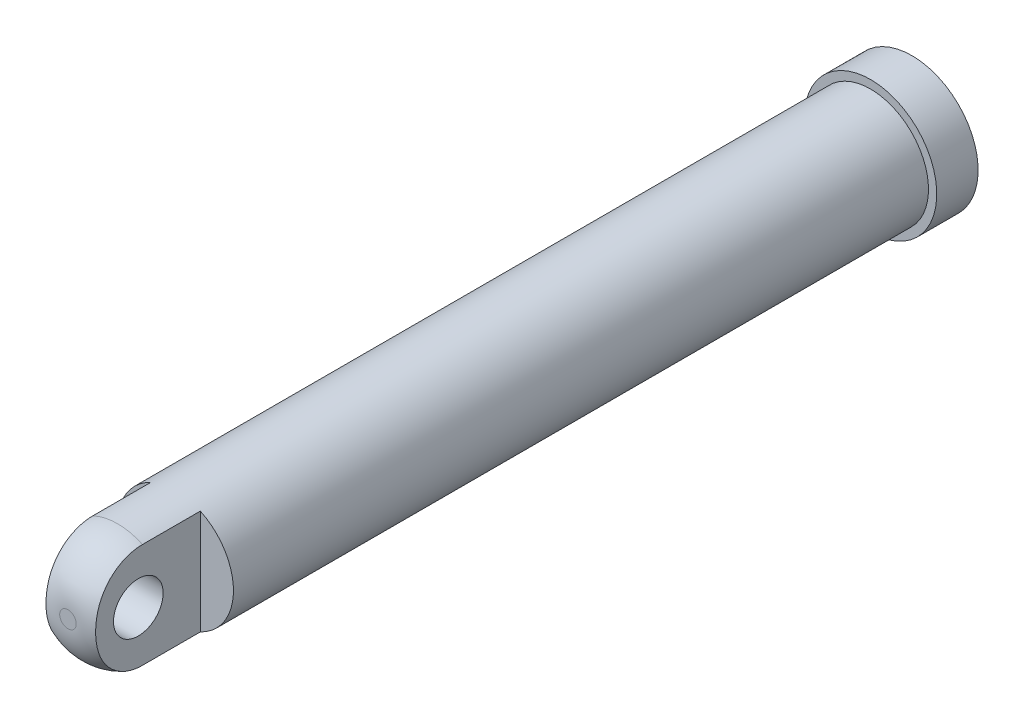
SolidWorks part; units mm, degrees
ref_plane "前视基准面" through (0, 0, 0) normal (0, 0, 1) x (1, 0, 0)
ref_plane "上视基准面" through (0, 0, 0) normal (0, 1, 0) x (1, 0, 0)
ref_plane "右视基准面" through (0, 0, 0) normal (1, 0, 0) x (0, 0, -1)
sketch "草图1" plane through (0, 0, 0) normal (0, 0, 1) x (1, 0, 0)
  circle A0 centre (0, 0) radius 70
extrude "凸台-拉伸2" add sketch "草图1" along normal blind 1150
sketch "草图2" plane through (0, 0, 1150) normal (0, 0, 1) x (1, 0, 0)
  line L0 (-30, 70) -> (-124.0556, 32.9777)
  line L1 (-30, 70) -> (-30, -70)
  line L2 (30, 70) -> (30, -70)
  line L4 (30, 70) -> (102.0705, 29.2659)
  line L5 (102.0705, 29.2659) -> (78.3722, -60.6733)
  line L6 (78.3722, -60.6733) -> (30, -70)
  line L7 (30, -70) -> (29.5481, -69.8099)
  line L8 (-30, -70) -> (-96.5186, -70)
  line L9 (-96.5186, -70) -> (-124.0556, 32.9777)
  circle M1 centre (0, 0) radius 70
extrude "切除-拉伸1" cut sketch "草图2" against normal blind 130 contours L2 M1 | L1 M1 region at (-46.4707, 0, 1150) region at (46.4707, 0, 1150)
sketch "草图3" plane through (30, 0, 0) normal (1, 0, 0) x (0, 0, -1)
  line L0 (-1150, 63.2456) -> (-1150, -63.2456) construction
  circle A0 centre (-1095, 0) radius 30
  point P2 (-1150, 0)
  dimension "D1" = 55
extrude "切除-拉伸2" cut sketch "草图3" against normal blind 130
fillet "圆角1" radius 60 1 edges at (0, 70, 1150)
sketch "草图4" plane through (0, 0, 0) normal (0, 0, -1) x (-1, 0, 0)
  circle A0 centre (0, 0) radius 50
extrude "切除-拉伸3" cut sketch "草图4" against normal blind 977
sketch "草图5" plane through (0, 0, 0) normal (0, 0, -1) x (-1, 0, 0)
  circle A0 centre (0, 0) radius 79.8496
extrude "切除-拉伸4" cut sketch "草图5" against normal blind 100
sketch "草图6" plane through (0, 0, 100) normal (0, 0, -1) x (-1, 0, 0)
  circle A0 centre (0, 0) radius 77.9741
extrude "切除-拉伸5" cut sketch "草图6" against normal blind 30
sketch "草图7" plane through (0, 0, 130) normal (0, 0, -1) x (-1, 0, 0)
  circle A0 centre (0, 0) radius 80
  circle A1 centre (0, 0) radius 70
  dimension "D1" = 160
extrude "凸台-拉伸4" add sketch "草图7" against normal blind 50
scale "缩放比例1" scale about origin uniform scaling yes scale factor 0.345
